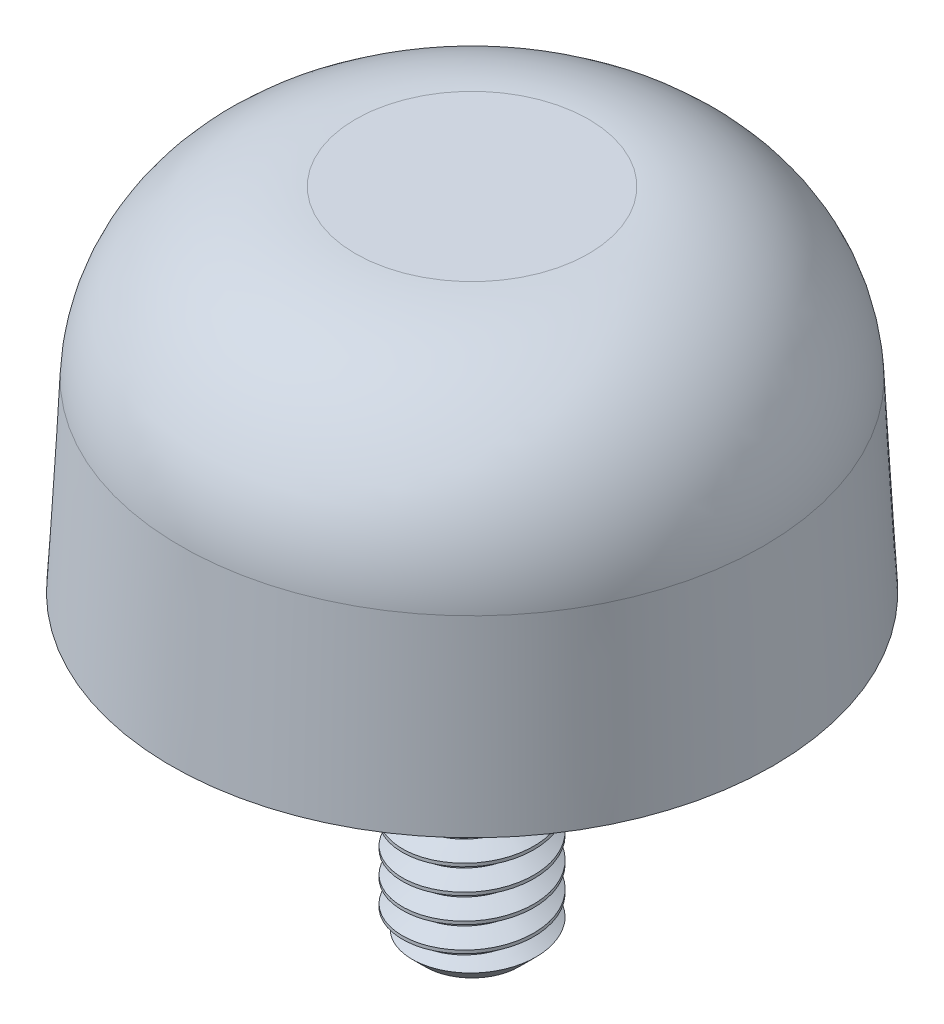
SolidWorks part; units mm, degrees
ref_plane "Front Plane" through (0, 0, 0) normal (0, 0, 1) x (1, 0, 0)
ref_plane "Top Plane" through (0, 0, 0) normal (0, 1, 0) x (1, 0, 0)
ref_plane "Right Plane" through (0, 0, 0) normal (1, 0, 0) x (0, 0, -1)
sketch "Sketch1" plane through (0, 0, 0) normal (0, 0, 1) x (1, 0, 0)
  line L0 (0, 0) -> (0, 11.1125) construction
  line L1 (0, 0) -> (0, -9.525) construction
  line L2 (-9.525, 0) -> (9.525, 0) construction
  line L3 (2.0828, -9.525) -> (-2.0828, -9.525) construction
  point P7 (0, 0)
  point P10 (0, -9.525)
sketch "Sketch2" plane through (0, 0, 0) normal (0, 0, 1) x (1, 0, 0)
  line L0 (0, -9.525) -> (0, 11.1125)
  line L1 (0, 11.1125) -> (3.688, 11.1125)
  line L2 (9.2176, 5.8651) -> (9.525, 0)
  line L3 (9.525, 0) -> (2.0828, 0)
  line L4 (-9.525, 0) -> (9.525, 0) construction
  line L5 (2.0828, 0) -> (2.0828, -9.525)
  line L6 (2.0828, -9.525) -> (0, -9.525)
  arc A1 (9.2176, 5.8651) -> (3.688, 11.1125) centre (3.688, 5.5753) ccw
  dimension "Bumper Radius" = 5.5372
  dimension "D1" = 3
revolve "Revolve1" add sketch "Sketch2" angle 360 about L0
sketch "Sketch3" plane through (0, -9.525, 0) normal (0, -1, 0) x (1, 0, 0)
  circle A0 centre (0, 0) radius 2.0828 construction
  circle A1 centre (0, 0) radius 2.0828
curve "Helix/Spiral1" pitch 0.7937 height 10.3187 radius 2.0828 centre (0, -9.525, 0) axis (0, 1, 0) start towards (-1, 0, 0) parameters "Pitch"=0.7937
sketch "Sketch4" plane through (0, 0, 0) normal (0, 0, 1) x (1, 0, 0)
  line L0 (-2.0828, -9.525) -> (-2.0828, -10.2195)
  line L1 (-2.0828, -10.2195) -> (-1.5672, -9.9219)
  line L2 (-1.5672, -9.9219) -> (-1.5672, -9.8227)
  line L3 (-1.5672, -9.8227) -> (-2.0828, -9.525)
  line L4 (-1.5672, -9.8723) -> (-2.0828, -9.8723) construction
  line L5 (-1.825, -9.6738) -> (-1.825, -10.0707) construction
  dimension "D1" = 60
  dimension "D2" = 0.3969
  dimension "D3" = 0.0992
chamfer "Chamfer1" distance 0.5953 angle 45 1 edges at (2.0828, -9.525, 0)
sweep "Cut-Sweep1" cut profiles "Sketch4" path "Helix/Spiral1"
equation "\"D3@Helix/Spiral1\"=\"Thread Length@Sketch1\"+\"Pitch@Helix/Spiral1\""
equation "\"D2@Sketch4\"=\"Pitch@Helix/Spiral1\"*.5"
equation "\"D3@Sketch4\"=\"Pitch@Helix/Spiral1\"*.125"
equation "\"D1@Chamfer1\"=\"Pitch@Helix/Spiral1\"*.75"
